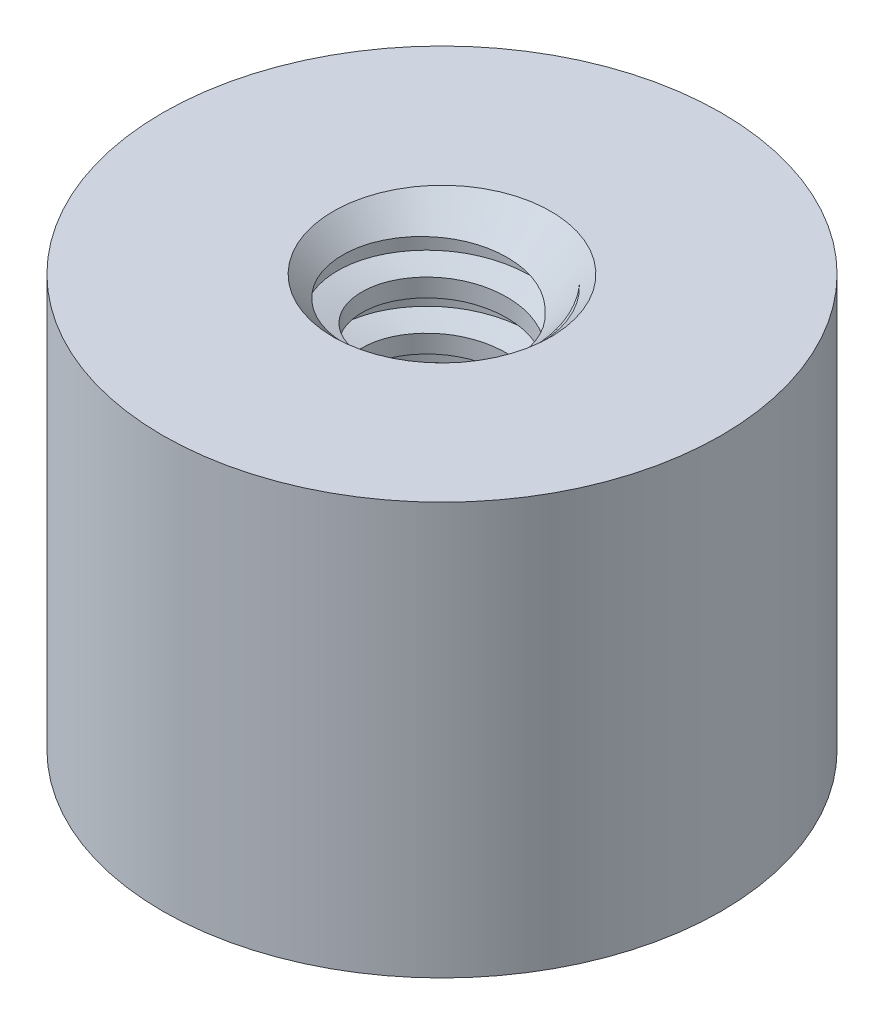
SolidWorks part; units mm, degrees
ref_plane "Front" through (0, 0, 0) normal (0, 0, 1) x (1, 0, 0)
ref_plane "Top" through (0, 0, 0) normal (0, 1, 0) x (1, 0, 0)
ref_plane "Right" through (0, 0, 0) normal (1, 0, 0) x (0, 0, -1)
sketch "Sketch1" plane through (0, 0, 0) normal (0, 1, 0) x (1, 0, 0)
  circle A0 centre (0, 0) radius 3.175
  circle A1 centre (0, 0) radius 9.1281
  dimension "ThreadDia" = 6.35
  dimension "OD" = 18.2562
extrude "Boss-Extrude1" add sketch "Sketch1" along normal mid plane 13.462
sketch "Sketch2" plane through (0, 6.731, 0) normal (0, 1, 0) x (1, 0, 0)
  circle A1 centre (0, 0) radius 3.175
  circle A2 centre (0, 0) radius 3.175 construction
curve "Helix/Spiral1" pitch 1.5875 height 15.0495 radius 3.175 centre (0, 6.731, 0) axis (0, -1, 0) start towards (1, 0, 0) parameters "Pitch"=1.5875
sketch "Sketch3" plane through (0, 0, 0) normal (0, 0, 1) x (1, 0, 0)
  line L0 (3.175, 6.731) -> (2.3813, 6.9363)
  line L2 (2.3813, 6.9363) -> (2.3813, 7.5248)
  line L3 (2.3813, 7.5248) -> (3.175, 7.73)
  line L4 (3.175, 7.73) -> (3.175, 6.731)
  line L5 (2.7782, 6.8336) -> (2.7782, 7.6274) construction
  line L6 (2.7782, 7.2305) -> (2.3813, 7.2305) construction
  line L7 (3.175, 6.731) -> (-3.175, 6.731) construction
  line L8 (9.1281, 6.731) -> (-9.1281, 6.731) construction
  spline S0 degree 3 poles (3.175, 6.731) (3.175, 6.698) (3.0082, 6.6312) (2.2959, 6.5317) (1.231, 6.432) (-0.023, 6.3323) (-1.2735, 6.2327) (-2.3284, 6.133) (-3.0256, 6.0333) (-3.2581, 5.9337) (-2.9902, 5.834) (-2.2629, 5.7343) (-1.1881, 5.6347) (0.0691, 5.535) (1.3158, 5.4353) (2.3604, 5.3357) (3.0424, 5.236) (3.2571, 5.1364) (2.9715, 5.0367) (2.2295, 4.937) (1.1451, 4.8374) (-0.1152, 4.7377) (-1.3579, 4.638) (-2.3919, 4.5384) (-3.0586, 4.4387) (-3.2555, 4.339) (-2.9523, 4.2394) (-2.1957, 4.1397) (-1.1018, 4.04) (0.1613, 3.9404) (1.3996, 3.8407) (2.423, 3.741) (3.0742, 3.6414) (3.2532, 3.5417) (2.9325, 3.442) (2.1614, 3.3424) (1.0583, 3.2427) (-0.2073, 3.143) (-1.4411, 3.0434) (-2.4536, 2.9437) (-3.0892, 2.844) (-3.2503, 2.7444) (-2.9121, 2.6447) (-2.1267, 2.545) (-1.0146, 2.4454) (0.2533, 2.3457) (1.4823, 2.246) (2.4837, 2.1464) (3.1035, 2.0467) (3.2467, 1.9471) (2.8912, 1.8474) (2.0916, 1.7477) (0.9707, 1.6481) (-0.2992, 1.5484) (-1.5232, 1.4487) (-2.5132, 1.3491) (-3.1172, 1.2494) (-3.2424, 1.1497) (-2.8696, 1.0501) (-2.056, 0.9504) (-0.9266, 0.8507) (0.3451, 0.7511) (1.5638, 0.6514) (2.5423, 0.5517) (3.1304, 0.4521) (3.2376, 0.3524) (2.8475, 0.2527) (2.0201, 0.1531) (0.8823, 0.0534) (-0.3909, -0.0463) (-1.6041, -0.1459) (-2.5709, -0.2456) (-3.1428, -0.3453) (-3.232, -0.4449) (-2.8248, -0.5446) (-1.9837, -0.6443) (-0.8379, -0.7439) (0.4366, -0.8436) (1.6441, -0.9432) (2.599, -1.0429) (3.1547, -1.1426) (3.2259, -1.2422) (2.8015, -1.3419) (1.9469, -1.4416) (0.7933, -1.5412) (-0.4823, -1.6409) (-1.6837, -1.7406) (-2.6265, -1.8402) (-3.1659, -1.9399) (-3.219, -2.0396) (-2.7777, -2.1392) (-1.9098, -2.2389) (-0.7485, -2.3386) (0.5278, -2.4382) (1.723, -2.5379) (2.6535, -2.6376) (3.1765, -2.7372) (3.2116, -2.8369) (2.7533, -2.9366) (1.8722, -3.0362) (0.7035, -3.1359) (-0.5732, -3.2356) (-1.7619, -3.3352) (-2.68, -3.4349) (-3.1865, -3.5346) (-3.2035, -3.6342) (-2.7284, -3.7339) (-1.8343, -3.8335) (-0.6584, -3.9332) (0.6186, -4.0329) (1.8005, -4.1325) (2.706, -4.2322) (3.1958, -4.3319) (3.1947, -4.4315) (2.7029, -4.5312) (1.796, -4.6309) (0.6132, -4.7305) (-0.6638, -4.8302) (-1.8388, -4.9299) (-2.7314, -5.0295) (-3.2044, -5.1292) (-3.1853, -5.2289) (-2.6769, -5.3285) (-1.7574, -5.4282) (-0.5679, -5.5279) (0.7088, -5.6275) (1.8767, -5.7272) (2.7562, -5.8269) (3.2125, -5.9265) (3.1753, -6.0262) (2.6504, -6.1259) (1.7184, -6.2255) (0.5224, -6.3252) (-0.7537, -6.4249) (-1.9142, -6.5245) (-2.7806, -6.6242) (-3.2199, -6.7239) (-3.1646, -6.8235) (-2.6233, -6.9232) (-1.679, -7.0228) (-0.4769, -7.1225) (0.7985, -7.2222) (1.9513, -7.3218) (2.8043, -7.4215) (3.2266, -7.5212) (3.1533, -7.6208) (2.5957, -7.7205) (1.6394, -7.8202) (0.4312, -7.9198) (-0.8431, -8.0195) (-1.988, -8.1192) (-2.8273, -8.2187) (-3.098, -8.2855) (-3.15, -8.3185) knots 0 0 0 0 0.006623 0.013245 0.019868 0.02649 0.033113 0.039735 0.046358 0.05298 0.059603 0.066225 0.072848 0.07947 0.086093 0.092715 0.099338 0.10596 0.112583 0.119205 0.125828 0.13245 0.139073 0.145695 0.152318 0.15894 0.165563 0.172185 0.178808 0.18543 0.192053 0.198675 0.205298 0.211921 0.218543 0.225166 0.231788 0.238411 0.245033 0.251656 0.258278 0.264901 0.271523 0.278146 0.284768 0.291391 0.298013 0.304636 0.311258 0.317881 0.324503 0.331126 0.337748 0.344371 0.350993 0.357616 0.364238 0.370861 0.377483 0.384106 0.390728 0.397351 0.403974 0.410596 0.417219 0.423841 0.430464 0.437086 0.443709 0.450331 0.456954 0.463576 0.470199 0.476821 0.483444 0.490066 0.496689 0.503311 0.509934 0.516556 0.523179 0.529801 0.536424 0.543046 0.549669 0.556291 0.562914 0.569536 0.576159 0.582781 0.589404 0.596026 0.602649 0.609272 0.615894 0.622517 0.629139 0.635762 0.642384 0.649007 0.655629 0.662252 0.668874 0.675497 0.682119 0.688742 0.695364 0.701987 0.708609 0.715232 0.721854 0.728477 0.735099 0.741722 0.748344 0.754967 0.761589 0.768212 0.774834 0.781457 0.788079 0.794702 0.801325 0.807947 0.81457 0.821192 0.827815 0.834437 0.84106 0.847682 0.854305 0.860927 0.86755 0.874172 0.880795 0.887417 0.89404 0.900662 0.907285 0.913907 0.92053 0.927152 0.933775 0.940397 0.94702 0.953642 0.960265 0.966887 0.97351 0.980132 0.986755 0.993377 1 1 1 1 construction
  dimension "D1" = 29
  dimension "D2" = 0.5885
  dimension "D3" = 0.7937
sketch "Sketch4" plane through (0, 6.731, 0) normal (0, 1, 0) x (1, 0, 0)
  circle A0 centre (0, 0) radius 3.556
  circle A2 centre (0, 0) radius 3.175 construction
  dimension "D1" = 0.381
sketch "Sketch5" plane through (0, -6.731, 0) normal (0, -1, 0) x (1, 0, 0)
  circle A1 centre (0, 0) radius 3.556
  circle A2 centre (0, 0) radius 3.556
  dimension "D1" = 0
sweep "Sweep1" add profiles "Sketch3" path "Helix/Spiral1"
extrude "Cut-Extrude1" cut sketch "Sketch4" along normal through all
extrude "Cut-Extrude2" cut sketch "Sketch5" along normal through all
extrude "Cut-Extrude3" cut sketch "Sketch4<2>" against normal through all draft 45
sketch "Sketch4<2>" plane through (0, 6.731, 0) normal (0, 1, 0) x (1, 0, 0) same geometry as "Sketch4"
extrude "Cut-Extrude4" cut sketch "Sketch5<2>" against normal through all draft 45
sketch "Sketch5<2>" plane through (0, -6.731, 0) normal (0, -1, 0) x (1, 0, 0) same geometry as "Sketch5"
equation "\"D3@Helix/Spiral1\" = \"Height@Boss-Extrude1\"+\"Pitch@Helix/Spiral1\""
equation "\"D2@Sketch3\" = \"Pitch@Helix/Spiral1\"*.3707"
equation "\"D3@Sketch3\" = \"Pitch@Helix/Spiral1\"*.5"
